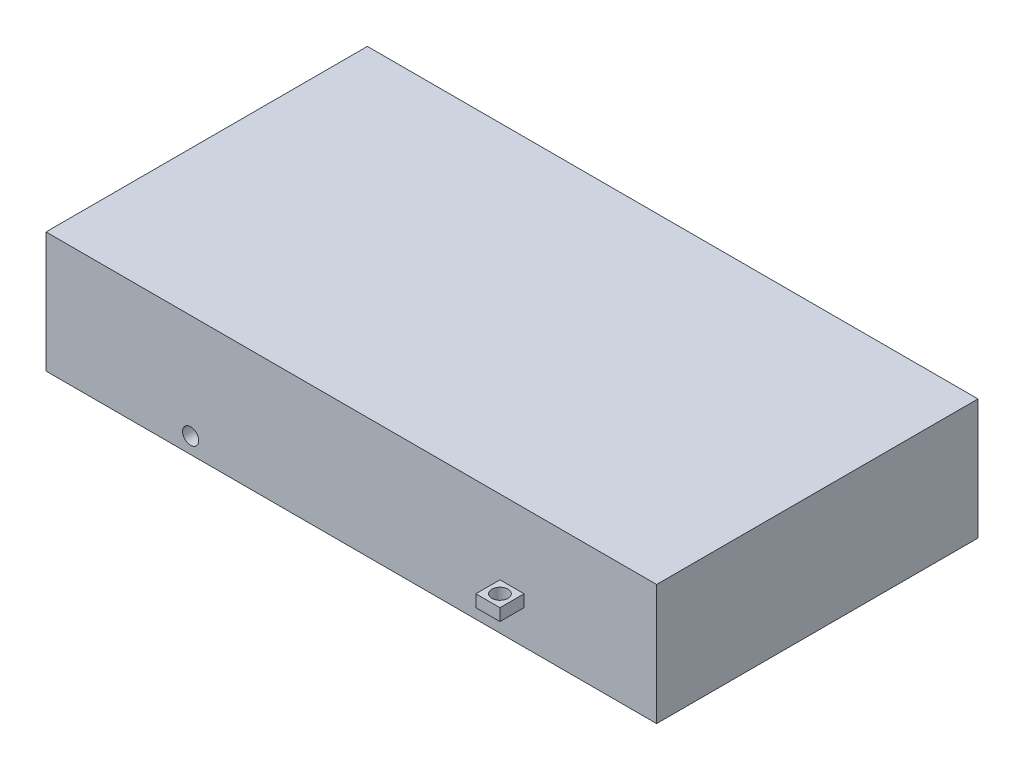
SolidWorks part; units mm, degrees
ref_plane "Front Plane" through (0, 0, 0) normal (0, 0, 1) x (1, 0, 0)
ref_plane "Top Plane" through (0, 0, 0) normal (0, 1, 0) x (1, 0, 0)
ref_plane "Right Plane" through (0, 0, 0) normal (1, 0, 0) x (0, 0, -1)
sketch "Sketch1" plane through (0, 0, 0) normal (0, 1, 0) x (1, 0, 0)
  line L1 (-482.6, -254) -> (482.6, -254)
  line L2 (-482.6, -254) -> (-482.6, 254)
  line L3 (-482.6, 254) -> (482.6, 254)
  line L4 (482.6, -254) -> (482.6, 254)
  line L5 (-482.6, -254) -> (482.6, 254) construction
  line L6 (-482.6, 254) -> (482.6, -254) construction
  point P0 (0, 0)
  dimension "D1" = 965.2
  dimension "D2" = 508
extrude "Boss-Extrude1" add sketch "Sketch1" along normal blind 190.5
sketch "Sketch2" plane through (0, 0, 254) normal (0, 0, 1) x (1, 0, 0)
  line L1 (234.95, 53.975) -> (273.05, 53.975)
  line L2 (234.95, 53.975) -> (234.95, 73.025)
  line L3 (234.95, 73.025) -> (273.05, 73.025)
  line L4 (273.05, 53.975) -> (273.05, 73.025)
  line L5 (234.95, 53.975) -> (273.05, 73.025) construction
  line L6 (234.95, 73.025) -> (273.05, 53.975) construction
  line L7 (-482.6, 190.5) -> (-482.6, 0) construction
  line L8 (-482.6, 0) -> (482.6, 0) construction
  circle A0 centre (-254, 25.4) radius 12.7
  point P0 (254, 63.5)
  dimension "D4" = 25.4
  dimension "D1" = 508
  dimension "D2" = 228.6
  dimension "D3" = 25.4
  dimension "D5" = 38.1
  dimension "D6" = 38.1
  dimension "D7" = 19.05
extrude "Boss-Extrude3" add sketch "Sketch2" along normal blind 38.1 contours L3 L4 L1 L2
sketch "Sketch3" plane through (0, 73.025, 0) normal (0, 1, 0) x (1, 0, 0)
  line L0 (234.95, -292.1) -> (273.05, -292.1) construction
  line L2 (234.95, -292.1) -> (234.95, -254) construction
  circle A0 centre (254, -273.05) radius 12.7
  dimension "D1" = 25.4
  dimension "D2" = 19.05
  dimension "D3" = 19.05
extrude "Cut-Extrude1" cut sketch "Sketch3" against normal up to next
extrude "Cut-Extrude2" cut sketch "Sketch2<4>" against normal up to next contours A0
sketch "Sketch2<4>" plane through (0, 0, 254) normal (0, 0, 1) x (1, 0, 0) same geometry as "Sketch2"
mirror "Mirror2" about plane through (0, 0, 0) normal (0, 0, 1) of "Boss-Extrude3", "Cut-Extrude1"
